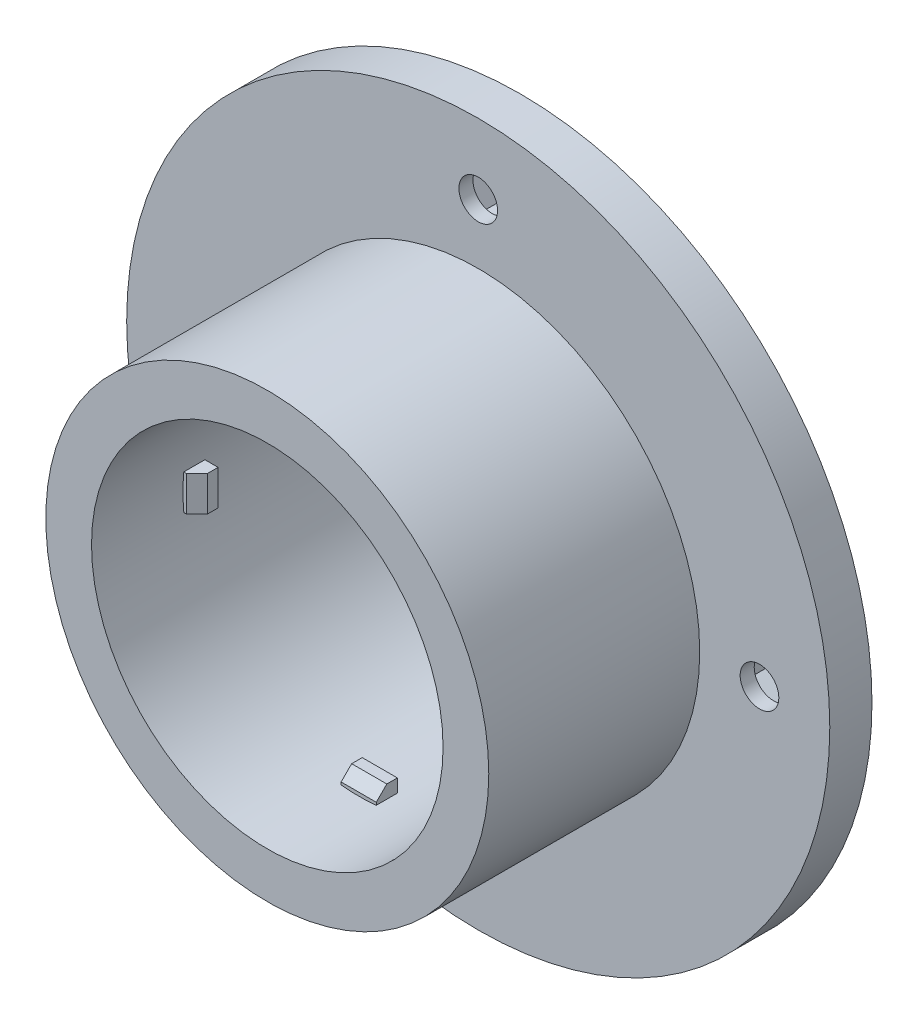
SolidWorks part; units mm, degrees
ref_plane "Płaszczyzna przednia" through (0, 0, 0) normal (0, 0, 1) x (1, 0, 0)
ref_plane "Płaszczyzna górna" through (0, 0, 0) normal (0, 1, 0) x (1, 0, 0)
ref_plane "Płaszczyzna prawa" through (0, 0, 0) normal (1, 0, 0) x (0, 0, -1)
sketch "Szkic1" plane through (0, 0, 0) normal (0, 0, 1) x (1, 0, 0)
  circle A1 centre (0, 0) radius 50
  dimension "D2" = 100
extrude "Dodanie-wyciągnięcie1" add sketch "Szkic1" along normal blind 6
sketch "Szkic2" plane through (0, 0, 6) normal (0, 0, 1) x (1, 0, 0)
  circle A0 centre (0, 0) radius 31.5
  dimension "D1" = 63
extrude "Dodanie-wyciągnięcie2" add sketch "Szkic2" along normal blind 30
sketch "Szkic3" plane through (0, 0, 36) normal (0, 0, 1) x (1, 0, 0)
  circle A0 centre (0, 0) radius 25
  dimension "D1" = 50
extrude "Wytnij-wyciągnięcie1" cut sketch "Szkic3" against normal through all
ref_plane "Płaszczyzna1" through (0, 0, 20) normal (0, 0, 1) x (1, 0, 0)
sketch "Szkic4" plane through (0, 0, 20) normal (0, 0, 1) x (1, 0, 0)
  line L0 (0, 25) -> (0, -25) construction
  line L1 (2.5, 23) -> (-2.5, 23)
  line L2 (-2.5, 23) -> (-2.5, 28)
  line L3 (-2.5, 28) -> (2.5, 28)
  line L4 (2.5, 28) -> (2.5, 23)
  circle A0 centre (0, 0) radius 25 construction
  point P8 (0, 23)
  dimension "D1" = 5
  dimension "D2" = 2
  dimension "D3" = 5
extrude "Dodanie-wyciągnięcie3" add sketch "Szkic4" along normal blind 3
fillet "Sfazowanie2" radius 1.5 1 edges at (0, 23, 23) type face fillet profile chamfer first side face at (0, 23.9687, 23) second side face at (0, 23, 21.5)
pattern_circular "Szyk kołowy3" count 4 over 360 about axis through (0, 0, 36) along (0, 0, 1) of "Dodanie-wyciągnięcie3", "Sfazowanie2"
sketch "Szkic5" plane through (0, 0, 0) normal (0, 0, -1) x (-1, 0, 0)
  line L0 (0, -50) -> (0, 50) construction
  line L1 (40, -4.9075) -> (44.25, -2.4537)
  line L2 (4.9075, 40) -> (2.4537, 44.25)
  line L3 (2.4537, 44.25) -> (-2.4537, 44.25)
  line L4 (-2.4537, 44.25) -> (-4.9075, 40)
  line L5 (-4.9075, 40) -> (-2.4537, 35.75)
  line L6 (-2.4537, 35.75) -> (2.4537, 35.75)
  line L7 (2.4537, 35.75) -> (4.9075, 40)
  line L8 (44.25, -2.4537) -> (44.25, 2.4537)
  line L9 (44.25, 2.4537) -> (40, 4.9075)
  line L10 (40, 4.9075) -> (35.75, 2.4537)
  line L11 (35.75, 2.4537) -> (35.75, -2.4537)
  line L12 (35.75, -2.4537) -> (40, -4.9075)
  line L13 (-4.9075, -40) -> (-2.4537, -44.25)
  line L14 (-2.4537, -44.25) -> (2.4537, -44.25)
  line L15 (2.4537, -44.25) -> (4.9075, -40)
  line L16 (4.9075, -40) -> (2.4537, -35.75)
  line L17 (2.4537, -35.75) -> (-2.4537, -35.75)
  line L18 (-2.4537, -35.75) -> (-4.9075, -40)
  line L19 (-40, 4.9075) -> (-44.25, 2.4537)
  line L20 (-44.25, 2.4537) -> (-44.25, -2.4537)
  line L21 (-44.25, -2.4537) -> (-40, -4.9075)
  line L22 (-40, -4.9075) -> (-35.75, -2.4537)
  line L23 (-35.75, -2.4537) -> (-35.75, 2.4537)
  line L24 (-35.75, 2.4537) -> (-40, 4.9075)
  circle A0 centre (0, 0) radius 50 construction
  circle A1 centre (0, 40) radius 4.25 construction
  dimension "D1" = 8.5
  dimension "D2" = 40
  dimension "D3" = 4
extrude "Wytnij-wyciągnięcie2" cut sketch "Szkic5" against normal blind 4
sketch "Szkic6" plane through (0, 0, 4) normal (0, 0, -1) x (-1, 0, 0)
  circle A0 centre (0, 40) radius 2.75
  circle A1 centre (40, 0) radius 2.75
  circle A2 centre (0, -40) radius 2.75
  circle A3 centre (-40, 0) radius 2.75
  dimension "D1" = 5.5
  dimension "D2" = 40
  dimension "D3" = 4
extrude "Wytnij-wyciągnięcie3" cut sketch "Szkic6" against normal through all
